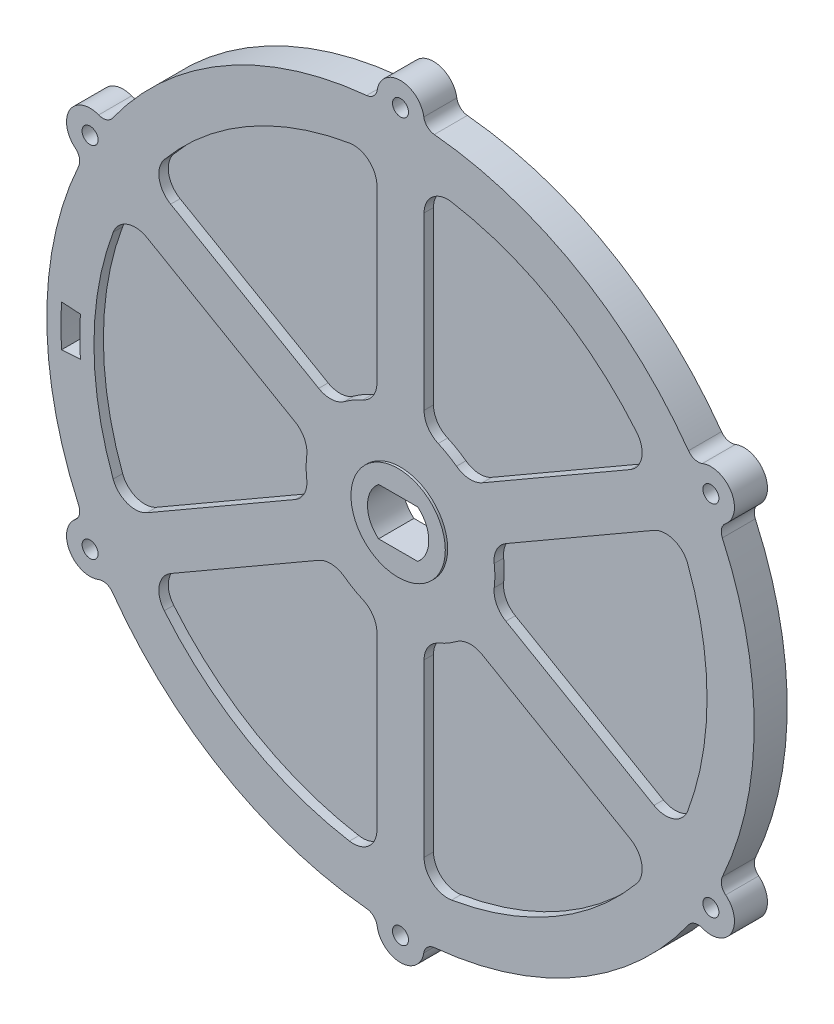
SolidWorks part; units mm, degrees
ref_plane "Front Plane" through (0, 0, 0) normal (0, 0, 1) x (1, 0, 0)
ref_plane "Top Plane" through (0, 0, 0) normal (0, 1, 0) x (1, 0, 0)
ref_plane "Right Plane" through (0, 0, 0) normal (1, 0, 0) x (0, 0, -1)
sketch "Sketch2" plane through (0, 0, 0) normal (0, 0, 1) x (1, 0, 0)
  line L0 (4.1533, 5) -> (-4.1533, 5)
  line L1 (4.1533, -5) -> (-4.1533, -5)
  circle A0 centre (0, 0) radius 75
  circle A1 centre (0, 0) radius 6.5
  dimension "D1" = 150
  dimension "D2" = 13
  dimension "D3" = 10
extrude "Boss-Extrude1" add sketch "Sketch2" along normal mid plane 7 contours A0 A1 | L0 A1 | L1 A1 region at (0, 5.6064, 0) region at (0, -5.6064, 0) region at (-72.8787, 0, 0)
sketch "Sketch3" plane through (0, 0, 3.5) normal (0, 0, 1) x (1, 0, 0)
  circle A0 centre (0, 0) radius 10
  arc M2 (4.1533, 5) -> (4.1533, -5) centre (0, 0) cw
  line M3 (4.1533, -5) -> (-4.1533, -5)
  arc M4 (-4.1533, -5) -> (-4.1533, 5) centre (0, 0) cw
  line M5 (-4.1533, 5) -> (4.1533, 5)
  dimension "D1" = 20
extrude "Boss-Extrude2" add sketch "Sketch3" along normal blind 0.5 contours A0 M5 M2 M3 M4 region at (-9.7172, 0, 3.5)
sketch "Sketch4" plane through (0, 0, -3.5) normal (0, 0, 1) x (1, 0, 0)
  line L0 (5, 76) -> (5, 74.8331)
  line L1 (-5, 76) -> (-5, 74.8331)
  arc A0 (5, 76) -> (-5, 76) centre (0, 76) ccw
  circle A1 centre (0, 0) radius 75 construction
  circle A3 centre (0, 0) radius 75
  arc A4 (-5, 74.8331) -> (5, 74.8331) centre (0, 0) ccw
  circle M9 centre (0, 0) radius 75
  dimension "D1" = 5
  dimension "D2" = 76
  dimension "D3" = 0
extrude "Boss-Extrude3" add sketch "Sketch4" along normal up to surface (7 mm away) contours A0 L0 L1 M9 region at (0, 77.5604, -3.5) up to face at (10, 0, 3.5)
fillet "Fillet1" radius 2.5 2 edges at (-5, 74.8331, 0) (5, 74.8331, 0)
sketch "Sketch6" plane through (0, 0, -3.5) normal (0, 0, -1) x (-1, 0, 0)
  circle A0 centre (0, 76) radius 1.7
  arc A4 (4.9414, 76.7632) -> (-4.9414, 76.7632) centre (0, 76) ccw construction
  dimension "D1" = 3.4
extrude "Cut-Extrude1" cut sketch "Sketch6" against normal through all
pattern_circular "CirPattern1" count 6 over 360 about axis through (0, 0, -3.5) along (0, 0, 1) of "Boss-Extrude3", "Cut-Extrude1", "Fillet1"
sketch "Sketch7" plane through (0, 0, -3.5) normal (0, 0, -1) x (-1, 0, 0)
  line L0 (-5, 59.1608) -> (-5, 22.9129)
  line L1 (5, 59.1608) -> (5, 22.9129)
  line L2 (-5, 19.3649) -> (5, 19.3649) construction
  line L3 (48.7348, 33.9105) -> (17.3431, 15.7866)
  line L4 (53.7348, 25.2503) -> (22.3431, 7.1263)
  line L6 (53.7348, -25.2503) -> (22.3431, -7.1263)
  line L7 (48.7348, -33.9105) -> (17.3431, -15.7866)
  line L9 (5, -59.1608) -> (5, -22.9129)
  line L10 (-5, -59.1608) -> (-5, -22.9129)
  line L12 (-48.7348, -33.9105) -> (-17.3431, -15.7866)
  line L13 (-53.7348, -25.2503) -> (-22.3431, -7.1263)
  line L15 (-53.7348, 25.2503) -> (-22.3431, 7.1263)
  line L16 (-48.7348, 33.9105) -> (-17.3431, 15.7866)
  line L18 (0, 0) -> (8, 18.3303) construction
  line L19 (14.2705, 14.0126) -> (19.2705, 5.3523) construction
  line L20 (19.2705, -5.3523) -> (14.2705, -14.0126) construction
  line L21 (5, -19.3649) -> (-5, -19.3649) construction
  line L22 (-14.2705, -14.0126) -> (-19.2705, -5.3523) construction
  line L23 (-19.2705, 5.3523) -> (-14.2705, 14.0126) construction
  arc A0 (-8, 18.3303) -> (-11.8745, 16.0934) centre (0, 0) ccw
  arc A1 (-10.8333, 64.0909) -> (-50.0876, 41.4274) centre (0, 0) ccw
  arc A2 (5, 22.9129) -> (8, 18.3303) centre (10, 22.9129) ccw
  arc A3 (5, 59.1608) -> (10.8333, 64.0909) centre (10, 59.1608) cw
  arc A4 (-5, 59.1608) -> (-10.8333, 64.0909) centre (-10, 59.1608) ccw
  arc A5 (-5, 22.9129) -> (-8, 18.3303) centre (-10, 22.9129) cw
  arc A6 (22.3431, 7.1263) -> (19.8745, 2.2369) centre (24.8431, 2.7962) ccw
  arc A7 (53.7348, 25.2503) -> (60.921, 22.6635) centre (56.2348, 20.9201) cw
  arc A8 (48.7348, 33.9105) -> (50.0876, 41.4274) centre (46.2348, 38.2407) ccw
  arc A9 (17.3431, 15.7866) -> (11.8745, 16.0934) centre (14.8431, 20.1167) cw
  arc A10 (17.3431, -15.7866) -> (11.8745, -16.0934) centre (14.8431, -20.1167) ccw
  arc A11 (48.7348, -33.9105) -> (50.0876, -41.4274) centre (46.2348, -38.2407) cw
  arc A12 (53.7348, -25.2503) -> (60.921, -22.6635) centre (56.2348, -20.9201) ccw
  arc A13 (22.3431, -7.1263) -> (19.8745, -2.2369) centre (24.8431, -2.7962) cw
  arc A14 (-5, -22.9129) -> (-8, -18.3303) centre (-10, -22.9129) ccw
  arc A15 (-5, -59.1608) -> (-10.8333, -64.0909) centre (-10, -59.1608) cw
  arc A16 (5, -59.1608) -> (10.8333, -64.0909) centre (10, -59.1608) ccw
  arc A17 (5, -22.9129) -> (8, -18.3303) centre (10, -22.9129) cw
  arc A18 (-22.3431, -7.1263) -> (-19.8745, -2.2369) centre (-24.8431, -2.7962) ccw
  arc A19 (-53.7348, -25.2503) -> (-60.921, -22.6635) centre (-56.2348, -20.9201) cw
  arc A20 (-48.7348, -33.9105) -> (-50.0876, -41.4274) centre (-46.2348, -38.2407) ccw
  arc A21 (-17.3431, -15.7866) -> (-11.8745, -16.0934) centre (-14.8431, -20.1167) cw
  arc A22 (-17.3431, 15.7866) -> (-11.8745, 16.0934) centre (-14.8431, 20.1167) ccw
  arc A23 (-48.7348, 33.9105) -> (-50.0876, 41.4274) centre (-46.2348, 38.2407) cw
  arc A24 (-53.7348, 25.2503) -> (-60.921, 22.6635) centre (-56.2348, 20.9201) ccw
  arc A25 (-22.3431, 7.1263) -> (-19.8745, 2.2369) centre (-24.8431, 2.7962) cw
  arc A26 (11.8745, 16.0934) -> (8, 18.3303) centre (0, 0) ccw
  arc A27 (19.8745, -2.2369) -> (19.8745, 2.2369) centre (0, 0) ccw
  arc A28 (8, -18.3303) -> (11.8745, -16.0934) centre (0, 0) ccw
  arc A29 (-11.8745, -16.0934) -> (-8, -18.3303) centre (0, 0) ccw
  arc A30 (-19.8745, 2.2369) -> (-19.8745, -2.2369) centre (0, 0) ccw
  arc A31 (50.0876, 41.4274) -> (10.8333, 64.0909) centre (0, 0) ccw
  arc A32 (60.921, -22.6635) -> (60.921, 22.6635) centre (0, 0) ccw
  arc A33 (10.8333, -64.0909) -> (50.0876, -41.4274) centre (0, 0) ccw
  arc A34 (-50.0876, -41.4274) -> (-10.8333, -64.0909) centre (0, 0) ccw
  arc A35 (-60.921, 22.6635) -> (-60.921, -22.6635) centre (0, 0) ccw
  point P8 (0, 19.3649)
  dimension "D1" = 130
  dimension "D2" = 40
  dimension "D4" = 5
  dimension "D3" = 10
  dimension "D5" = 6
extrude "Cut-Extrude2" cut sketch "Sketch7" against normal blind 2
mirror "Mirror1" about plane through (0, 0, 0) normal (0, 0, 1) of "Cut-Extrude2"
sketch "Sketch9" plane through (0, 0, 0) normal (0, 1, 0) x (1, 0, 0)
  line L0 (-7.173, 3.5) -> (-61.0677, 3.5) construction
  line L1 (-72, -3.5) -> (-68, -3.5)
  line L2 (-72, -3.5) -> (-72, 3.5)
  line L3 (-72, 3.5) -> (-68, 3.5)
  line L4 (-68, -3.5) -> (-68, 3.5)
  line L5 (-61.0677, -3.5) -> (-7.173, -3.5) construction
  line L6 (0, 0) -> (0, 49.8627) construction
  dimension "D1" = 4
  dimension "D2" = 72
revolve "Cut-Revolve1" cut sketch "Sketch9" angle 7 mid plane about L6
